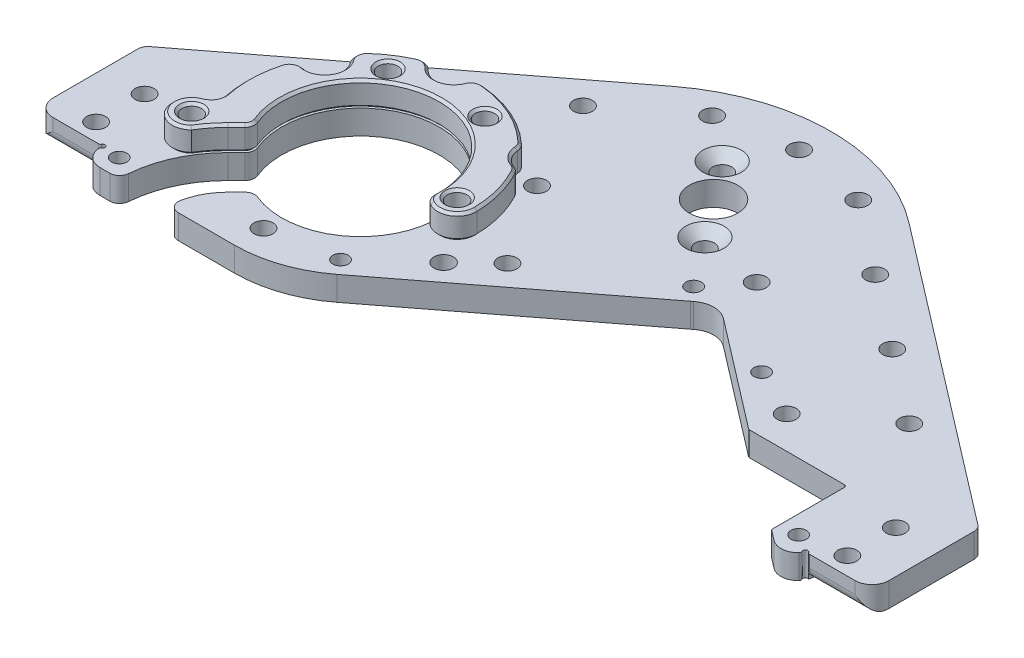
SolidWorks part; units mm, degrees
other "Weapon Motor Shock Spacer"
material "Alum Plate"
ref_plane "Front Plane" through (0, 0, 0) normal (0, 0, 1) x (1, 0, 0)
ref_plane "Top Plane" through (0, 0, 0) normal (0, 1, 0) x (1, 0, 0)
ref_plane "Right Plane" through (0, 0, 0) normal (1, 0, 0) x (0, 0, -1)
sketch "Top Layout" plane through (0, 0, 0) normal (0, 1, 0) x (1, 0, 0)
  line L0 (-114.046, -123.825) -> (-104.775, -123.825) construction
  line L1 (-104.775, -142.875) -> (-101.6, -142.875)
  line L2 (-104.775, -142.875) -> (-104.775, -104.775)
  line L3 (-104.775, -104.775) -> (-101.6, -104.775)
  line L4 (-101.6, -142.875) -> (-101.6, -104.775)
  line L5 (-104.775, -142.875) -> (-101.6, -104.775) construction
  line L6 (-104.775, -104.775) -> (-101.6, -142.875) construction
  line L7 (-19.05, -105.8164) -> (-101.6, -105.8164)
  line L8 (-19.05, -105.8164) -> (-19.05, -141.8336)
  line L9 (-19.05, -141.8336) -> (-101.6, -141.8336)
  line L10 (-101.6, -105.8164) -> (-101.6, -141.8336)
  line L11 (-19.05, -105.8164) -> (-101.6, -141.8336) construction
  line L12 (-19.05, -141.8336) -> (-101.6, -105.8164) construction
  line L13 (-133.096, -85.725) -> (-114.046, -85.725)
  line L14 (-133.096, -85.725) -> (-133.096, -161.925)
  line L15 (-133.096, -161.925) -> (-114.046, -161.925)
  line L16 (-114.046, -85.725) -> (-114.046, -161.925)
  line L17 (-133.096, -85.725) -> (-114.046, -161.925) construction
  line L18 (-133.096, -161.925) -> (-114.046, -85.725) construction
  line L19 (-104.775, -123.825) -> (0, -123.825) construction
  line L20 (0, -123.825) -> (0, 0) construction
  line L21 (-52.3528, -40.1717) -> (0, 0) construction
  line L22 (-70.6449, -16.3328) -> (-18.2922, 23.8388)
  line L23 (-34.0606, -64.0105) -> (18.2922, -23.8388)
  line L24 (-30.9251, 40.3023) -> (-122.2248, -29.7544)
  line L25 (-153.9748, -53.975) -> (-153.9748, -123.825)
  line L26 (-109.5248, -162.052) -> (109.5248, -162.052)
  line L27 (0, -162.052) -> (0, -123.825) construction
  line L28 (-109.5248, -162.052) -> (-109.5248, -20.0093) construction
  line L29 (-104.775, -142.875) -> (-104.775, -152.527)
  line L30 (-104.775, -152.527) -> (104.775, -152.527)
  line L31 (104.775, -104.775) -> (101.6, -104.775)
  line L32 (-144.4498, -73.025) -> (-109.5248, -73.025)
  line L33 (-144.4498, -73.025) -> (-144.4498, -123.825)
  line L34 (-144.4498, -123.825) -> (-109.5248, -123.825) construction
  line L35 (-109.5248, -73.025) -> (-109.5248, -162.052)
  line L36 (-144.4498, -73.025) -> (-109.5248, -123.825) construction
  line L37 (-144.4498, -123.825) -> (-109.5248, -73.025) construction
  line L38 (101.6, -142.875) -> (101.6, -104.775)
  line L39 (104.775, -142.875) -> (101.6, -142.875)
  line L40 (104.775, -142.875) -> (104.775, -104.775)
  line L41 (104.775, -142.875) -> (104.775, -152.527)
  line L42 (109.5248, -162.052) -> (109.5248, -20.0093) construction
  line L43 (30.9251, 40.3023) -> (122.2248, -29.7544)
  line L45 (19.05, -141.8336) -> (101.6, -141.8336)
  line L46 (101.6, -105.8164) -> (101.6, -141.8336)
  line L47 (19.05, -105.8164) -> (101.6, -105.8164)
  line L48 (19.05, -105.8164) -> (19.05, -141.8336)
  line L49 (133.096, -161.925) -> (114.046, -161.925)
  line L50 (114.046, -85.725) -> (114.046, -161.925)
  line L51 (133.096, -85.725) -> (114.046, -85.725)
  line L52 (133.096, -85.725) -> (133.096, -161.925)
  line L53 (144.4498, -123.825) -> (109.5248, -123.825) construction
  line L54 (109.5248, -73.025) -> (109.5248, -162.052)
  line L55 (144.4498, -73.025) -> (109.5248, -73.025)
  line L56 (144.4498, -73.025) -> (144.4498, -123.825)
  line L57 (-109.5248, -123.825) -> (-109.5248, -162.052) construction
  line L62 (-153.9748, -53.975) -> (-122.2248, -53.975)
  line L63 (-122.2248, -53.975) -> (-122.2248, -29.7544)
  line L64 (-144.4498, -123.825) -> (-153.9748, -123.825)
  line L65 (153.9748, -53.975) -> (153.9748, -123.825)
  line L66 (109.5248, -123.825) -> (109.5248, -162.052) construction
  line L67 (144.4498, -123.825) -> (153.9748, -123.825)
  line L68 (122.2248, -29.7544) -> (122.2248, -53.975)
  line L73 (-104.775, -104.775) -> (-104.775, -16.3647) construction
  line L74 (-95.25, -162.052) -> (-95.25, -9.0559) construction
  line L75 (-109.5248, -162.052) -> (-109.5248, -123.825) construction
  line L76 (109.5248, -162.052) -> (109.5248, -123.825) construction
  line L77 (122.2248, -53.975) -> (153.9748, -53.975)
  line L83 (104.775, -155.5496) -> (-104.775, -155.5496) construction
  line L88 (95.25, -162.052) -> (95.25, -9.0559) construction
  line L89 (104.775, -104.775) -> (104.775, -16.3647) construction
  line L92 (-104.775, -152.527) -> (-104.775, -162.052) construction
  line L93 (-14.605, -76.327) -> (14.605, -76.327)
  line L94 (-14.605, -76.327) -> (-14.605, -152.527)
  line L95 (-14.605, -152.527) -> (14.605, -152.527)
  line L96 (14.605, -76.327) -> (14.605, -152.527)
  line L97 (-14.605, -76.327) -> (14.605, -152.527) construction
  line L98 (-14.605, -152.527) -> (14.605, -76.327) construction
  line L99 (104.775, -152.527) -> (104.775, -162.052) construction
  line L100 (-19.05, -105.8164) -> (0, -105.8164) construction
  line L107 (0, -105.8164) -> (19.05, -105.8164) construction
  line L108 (104.775, -123.825) -> (114.046, -123.825) construction
  circle A0 centre (0, 0) radius 114.3
  circle A1 centre (0, 0) radius 6.35
  circle A2 centre (-52.3528, -40.1717) radius 17.8
  circle A3 centre (0, 0) radius 30.0482
  circle A4 centre (-52.3528, -40.1717) radius 30.0482
  arc A5 (-30.9251, 40.3023) -> (30.9251, 40.3023) centre (0, 0) cw
  point P2 (-103.1875, -123.825)
  point P7 (-60.325, -123.825)
  point P12 (-123.571, -123.825)
  point P30 (-126.9873, -98.425)
  point P35 (0, -114.427)
  point P53 (0, -152.527)
  dimension "D1" = 35.6
  dimension "D2" = 12.7
  dimension "D3" = 228.6
  dimension "D11" = 60.0964
  dimension "D12" = 50.8
  dimension "D14" = 52.5
  dimension "D4" = 3.175
  dimension "D5" = 19.05
  dimension "D6" = 76.2
  dimension "D7" = 82.55
  dimension "D8" = 38.1
  dimension "D9" = 104.775
  dimension "D10" = 18.0086
  dimension "D13" = 9.525
  dimension "D15" = 4.7498
  dimension "D16" = 9.525
  dimension "D17" = 9.652
  dimension "D18" = 50.8
  dimension "D19" = 12.446
  dimension "D20" = 65.9892
  dimension "D21" = 19.05
  dimension "D22" = 34.925
  dimension "D23" = 123.825
  dimension "D24" = 12.7
  dimension "D25" = 9.525
  dimension "D26" = 29.21
  dimension "D27" = 76.2
  dimension "D28" = 3.0226
sketch "Side Layout" plane through (0, 0, 0) normal (1, 0, 0) x (0, 0, -1)
  line L0 (0, -38.1) -> (0, 33.7344) construction
  line L1 (-114.3, -20.955) -> (114.3, -20.955)
  line L2 (-114.3, -20.955) -> (-114.3, -33.655)
  line L3 (-114.3, -33.655) -> (114.3, -33.655)
  line L4 (114.3, -20.955) -> (114.3, -33.655)
  line L5 (-114.3, -20.955) -> (114.3, -33.655) construction
  line L6 (-114.3, -33.655) -> (114.3, -20.955) construction
  line L7 (-9.525, -32.9406) -> (9.525, -32.9406)
  line L8 (-9.525, -32.9406) -> (-9.525, -38.1)
  line L9 (-9.525, -38.1) -> (9.525, -38.1)
  line L10 (9.525, -32.9406) -> (9.525, -38.1)
  line L11 (-9.525, -32.9406) -> (9.525, -38.1) construction
  line L12 (-9.525, -38.1) -> (9.525, -32.9406) construction
  line L13 (-11.9126, -29.3338) -> (11.9126, -29.3338)
  line L14 (-11.9126, -29.3338) -> (-11.9126, -32.9406)
  line L15 (-11.9126, -32.9406) -> (11.9126, -32.9406)
  line L16 (11.9126, -29.3338) -> (11.9126, -32.9406)
  line L17 (-11.9126, -29.3338) -> (11.9126, -32.9406) construction
  line L18 (-11.9126, -32.9406) -> (11.9126, -29.3338) construction
  line L19 (-6.35, -32.9406) -> (6.35, -32.9406)
  line L20 (-6.35, -32.9406) -> (-6.35, 33.7344)
  line L21 (-6.35, 33.7344) -> (6.35, 33.7344)
  line L22 (6.35, -32.9406) -> (6.35, 33.7344)
  line L23 (-6.35, -32.9406) -> (6.35, 33.7344) construction
  line L24 (-6.35, 33.7344) -> (6.35, -32.9406) construction
  line L25 (-162.052, 0) -> (-123.825, 0) construction
  line L26 (114.3, -33.655) -> (114.3, 0) construction
  line L27 (-142.875, 19.05) -> (-104.775, 19.05)
  line L28 (-40.1717, -9.525) -> (-40.1717, 5.4) construction
  line L29 (-142.875, 19.05) -> (-142.875, -19.05)
  line L30 (-142.875, -19.05) -> (-104.775, -19.05)
  line L31 (-104.775, 19.05) -> (-104.775, -19.05)
  line L32 (-142.875, 19.05) -> (-104.775, -19.05) construction
  line L33 (-142.875, -19.05) -> (-104.775, 19.05) construction
  line L34 (-130.175, -38.1) -> (-117.9516, -38.1) construction
  line L35 (-57.9717, -14.6) -> (-22.3717, -14.6)
  line L36 (-30.0482, -2.794) -> (30.0482, -2.794)
  line L37 (-30.0482, -2.794) -> (-30.0482, -20.955)
  line L38 (-30.0482, -20.955) -> (30.0482, -20.955)
  line L39 (30.0482, -2.794) -> (30.0482, -20.955)
  line L40 (-30.0482, -2.794) -> (30.0482, -20.955) construction
  line L41 (-30.0482, -20.955) -> (30.0482, -2.794) construction
  line L42 (-30.0482, -2.794) -> (-30.0482, 0) construction
  line L43 (-123.825, 0) -> (0, 0) construction
  line L44 (-57.9717, -14.6) -> (-57.9717, 25.4)
  line L45 (-57.9717, 25.4) -> (-22.3717, 25.4)
  line L46 (-22.3717, -14.6) -> (-22.3717, 25.4)
  line L47 (-19.05, 0) -> (19.05, 0)
  line L48 (-19.05, 0) -> (-19.05, -1.9812)
  line L49 (-19.05, -1.9812) -> (19.05, -1.9812)
  line L50 (19.05, 0) -> (19.05, -1.9812)
  line L51 (-19.05, 0) -> (19.05, -1.9812) construction
  line L52 (-19.05, -1.9812) -> (19.05, 0) construction
  line L53 (-70.2199, -3.175) -> (-10.1235, -3.175)
  line L54 (-70.2199, -3.175) -> (-70.2199, -15.875)
  line L55 (-70.2199, -15.875) -> (-10.1235, -15.875)
  line L56 (-10.1235, -3.175) -> (-10.1235, -15.875)
  line L57 (-70.2199, -3.175) -> (-10.1235, -15.875) construction
  line L58 (-70.2199, -15.875) -> (-10.1235, -3.175) construction
  line L59 (-40.1717, -9.525) -> (-40.1717, 0) construction
  line L60 (-57.9717, -14.6) -> (-22.3717, 25.4) construction
  line L61 (-57.9717, 25.4) -> (-22.3717, -14.6) construction
  line L62 (-22.3717, 0) -> (-57.9717, 0) construction
  line L63 (-137.8162, 0) -> (-123.825, -13.9912) construction
  line L64 (-139.065, 15.24) -> (-108.585, 15.24) construction
  line L65 (-139.065, 15.24) -> (-139.065, -15.24) construction
  line L66 (-139.065, -15.24) -> (-108.585, -15.24) construction
  line L67 (-108.585, 15.24) -> (-108.585, -15.24) construction
  line L68 (-139.065, 15.24) -> (-108.585, -15.24) construction
  line L69 (-139.065, -15.24) -> (-108.585, 15.24) construction
  line L70 (-137.8162, 0) -> (-123.825, 13.9912) construction
  line L71 (-123.825, -13.9912) -> (-109.8338, 0) construction
  line L72 (-123.825, 13.9912) -> (-109.8338, 0) construction
  line L73 (-137.8162, 0) -> (-109.8338, 0) construction
  line L74 (-123.825, -13.9912) -> (-123.825, 13.9912) construction
  line L75 (-6.35, 17.8594) -> (6.35, 17.8594)
  line L76 (114.3, 0) -> (-114.3, 0) construction
  line L77 (-22.3717, 19.05) -> (-6.35, 19.05) construction
  line L78 (-123.825, 38.1) -> (-97.9206, 38.1) construction
  line L79 (-19.05, -3.5814) -> (19.05, -3.5814)
  line L80 (-19.05, -3.5814) -> (-19.05, -1.9812)
  line L81 (-19.05, -1.9812) -> (19.05, -1.9812)
  line L82 (19.05, -3.5814) -> (19.05, -1.9812)
  line L83 (-19.05, -3.5814) -> (19.05, -1.9812) construction
  line L84 (-19.05, -1.9812) -> (19.05, -3.5814) construction
  line L85 (-8.7376, -16.7608) -> (8.7376, -16.7608)
  line L86 (-8.7376, -16.7608) -> (-8.7376, -29.3338)
  line L87 (-8.7376, -29.3338) -> (8.7376, -29.3338)
  line L88 (8.7376, -16.7608) -> (8.7376, -29.3338)
  line L89 (-8.7376, -16.7608) -> (8.7376, -29.3338) construction
  line L90 (-8.7376, -29.3338) -> (8.7376, -16.7608) construction
  line L91 (-8.7376, -3.5814) -> (8.7376, -3.5814)
  line L92 (-8.7376, -3.5814) -> (-8.7376, -16.1544)
  line L93 (-8.7376, -16.1544) -> (8.7376, -16.1544)
  line L94 (8.7376, -3.5814) -> (8.7376, -16.1544)
  line L95 (-8.7376, -3.5814) -> (8.7376, -16.1544) construction
  line L96 (-8.7376, -16.1544) -> (8.7376, -3.5814) construction
  circle A0 centre (-123.825, 0) radius 18.0086
  circle A1 centre (-123.825, 0) radius 38.1
  circle A2 centre (-139.065, 15.24) radius 1.905
  circle A3 centre (-108.585, 15.24) radius 1.905
  circle A4 centre (-108.585, -15.24) radius 1.905
  circle A5 centre (-139.065, -15.24) radius 1.905
  circle A6 centre (-137.8162, 0) radius 1.6002
  circle A7 centre (-123.825, 13.9912) radius 1.6002
  circle A8 centre (-109.8338, 0) radius 1.6002
  circle A9 centre (-123.825, -13.9912) radius 1.6002
  point P0 (0, -27.305)
  point P6 (0, -31.1372)
  point P7 (0, -35.5203)
  point P21 (0, 0.3969)
  point P32 (0, -11.8745)
  point P43 (0, -0.9906)
  point P55 (-40.1717, -9.525)
  point P72 (-40.1717, 5.4)
  point P88 (0, -23.0473)
  point P93 (0, -2.7813)
  point P102 (0, -9.8679)
  dimension "D17" = 3.81
  dimension "D18" = 3.2004
  dimension "D1" = 12.7
  dimension "D2" = 5.1594
  dimension "D3" = 19.05
  dimension "D4" = 3.6068
  dimension "D5" = 23.8252
  dimension "D6" = 12.7
  dimension "D7" = 18.161
  dimension "D8" = 1.9812
  dimension "D9" = 12.7
  dimension "D10" = 40
  dimension "D11" = 25.4
  dimension "D12" = 50.8
  dimension "D13" = 41.275
  dimension "D14" = 30.48
  dimension "D15" = 4.445
  dimension "D16" = 19.7866
  dimension "D19" = 15.875
  dimension "D20" = 6.35
  dimension "D21" = 38.1
  dimension "D22" = 1.6002
  dimension "D23" = 38.1
  dimension "D24" = 17.4752
  dimension "D25" = 12.573
ref_plane "Plane1" through (0, 25.4, 0) normal (0, 1, 0) x (1, 0, 0)
sketch "Sketch3" plane through (0, 25.4, 0) normal (0, 1, 0) x (1, 0, 0)
  line L0 (-104.775, -36.3747) -> (-30.9251, 20.2924)
  line L1 (-104.775, -104.775) -> (-104.775, -16.3647) construction
  line L2 (0, -200130.175) -> (0, 199882.0484) construction
  line L3 (-30.9251, 40.3023) -> (-122.2248, -29.7544) construction
  line L5 (-104.775, -36.3747) -> (-104.775, -77.6497)
  line L6 (-92.075, -77.6497) -> (-104.775, -77.6497)
  line L7 (30.9251, 20.2924) -> (104.775, -36.3747)
  line L8 (104.775, -77.6497) -> (92.075, -77.6497)
  line L9 (104.775, -36.3747) -> (104.775, -77.6497)
  line L11 (104.775, -104.775) -> (104.775, -16.3647) construction
  line L12 (30.9251, 40.3023) -> (122.2248, -29.7544) construction
  line L13 (92.075, -74.6536) -> (24.1423, -22.5271)
  line L14 (-32.2514, -66.3682) -> (20.1013, -26.1965)
  line L15 (-30.9251, 20.2924) -> (0, 44.022)
  line L16 (0, 44.022) -> (30.9251, 20.2924)
  line L17 (-92.075, -77.6497) -> (-92.075, -73.1917)
  line L19 (-92.075, -73.1917) -> (-52.3528, -73.1917)
  line L20 (92.075, -74.6536) -> (92.075, -77.6497)
  circle A1 centre (-52.3528, -40.1717) radius 20.6375
  circle A2 centre (0, 0) radius 6.35
  circle A3 centre (0, 0) radius 6.35 construction
  arc A4 (-52.3528, -73.1917) -> (-32.2514, -66.3682) centre (-52.3528, -40.1717) ccw
  arc A5 (20.1013, -26.1965) -> (24.1423, -22.5271) centre (0, 0) ccw
  arc A6 (30.9251, 20.2924) -> (-30.9251, 20.2924) centre (0, -20.01) ccw construction
  point P28 (0, 44.022)
  dimension "D1" = 33.02
  dimension "D5" = 50.8
  dimension "D7" = 41.275
  dimension "D2" = 41.275
  dimension "D3" = 34.925
  dimension "D4" = 12.7
  dimension "D6" = 38.1
extrude "Boss-Extrude1" add sketch "Sketch3" against normal blind 6.35
ref_plane "Plane3" through (-104.775, 0, 0) normal (-1, 0, 0) x (0, 0, 1)
sketch "Sketch6" plane through (-104.775, 0, 0) normal (-1, 0, 0) x (0, 0, 1)
  line L0 (162.052, -25.4) -> (162.052, 25.4)
  line L1 (162.052, 25.4) -> (77.6497, 25.4)
  line L2 (36.3747, 25.4) -> (77.6497, 25.4) construction
  line L3 (147.7645, 11.1125) -> (162.052, 11.1125) construction
  line L4 (162.052, 0) -> (71.2997, 0) construction
  line L5 (77.6497, 25.4) -> (77.6497, 19.05)
  line L6 (77.6497, 19.05) -> (36.3747, 19.05)
  line L7 (36.3747, 19.05) -> (36.3747, 6.35)
  line L8 (36.3747, 6.35) -> (71.2997, 6.35)
  line L10 (99.6315, -3.175) -> (99.6315, 11.1125) construction
  line L11 (71.2997, -25.4) -> (162.052, -25.4)
  line L13 (71.2997, 6.35) -> (71.2997, -25.4)
  line L14 (152.527, -25.4) -> (152.527, 25.4) construction
  line L15 (99.6315, 11.1125) -> (99.6315, 25.4) construction
  line L16 (147.7645, 11.1125) -> (147.7645, 25.4) construction
  line L17 (94.869, -7.9375) -> (104.394, -7.9375) construction
  line L18 (94.869, -7.9375) -> (94.869, 25.4) construction
  line L19 (94.869, 25.4) -> (104.394, 25.4) construction
  line L20 (104.394, -7.9375) -> (104.394, 25.4) construction
  line L21 (94.869, -7.9375) -> (104.394, 25.4) construction
  line L22 (94.869, 25.4) -> (104.394, -7.9375) construction
  line L23 (147.7645, 11.1125) -> (147.7645, -3.175) construction
  line L24 (104.394, -7.9375) -> (123.825, -7.9375) construction
  line L25 (143.002, -7.9375) -> (152.527, -7.9375) construction
  line L26 (143.002, -7.9375) -> (143.002, 25.4) construction
  line L27 (143.002, 25.4) -> (152.527, 25.4) construction
  line L28 (152.527, -7.9375) -> (152.527, 25.4) construction
  line L29 (143.002, -7.9375) -> (152.527, 25.4) construction
  line L30 (143.002, 25.4) -> (152.527, -7.9375) construction
  line L31 (123.825, -7.9375) -> (152.527, -7.9375) construction
  line L32 (104.775, 19.05) -> (104.775, -19.05) construction
  line L34 (155.702, -25.4) -> (155.702, 25.4) construction
  circle A0 centre (109.8338, 0) radius 1.6002 construction
  circle A1 centre (123.825, 13.9912) radius 1.6002 construction
  circle A2 centre (137.8162, 0) radius 1.6002 construction
  circle A3 centre (123.825, -13.9912) radius 1.6002 construction
  circle A4 centre (109.8338, 0) radius 1.6002 construction
  circle A5 centre (123.825, 13.9912) radius 1.6002 construction
  circle A6 centre (137.8162, 0) radius 1.6002 construction
  circle A7 centre (123.825, -13.9912) radius 1.6002 construction
  circle A8 centre (123.825, 0) radius 18.0086 construction
  circle A9 centre (123.825, 0) radius 18.0086 construction
  circle A10 centre (123.825, 0) radius 9.525
  circle A11 centre (108.585, -15.24) radius 1.905 construction
  circle A12 centre (108.585, 15.24) radius 1.905 construction
  circle A13 centre (139.065, 15.24) radius 1.905 construction
  circle A14 centre (139.065, -15.24) radius 1.905 construction
  circle A15 centre (108.585, -15.24) radius 1.905
  circle A16 centre (108.585, 15.24) radius 1.905
  circle A17 centre (139.065, 15.24) radius 1.905
  circle A18 centre (139.065, -15.24) radius 1.905
  circle A19 centre (147.7645, 11.1125) radius 2.5527
  circle A26 centre (99.6315, 11.1125) radius 2.5527
  circle A27 centre (99.6315, -3.175) radius 2.5527
  circle A28 centre (147.7645, -3.175) radius 2.5527
  point P29 (0, 0)
  point P55 (99.6315, 8.7312)
  point P61 (147.7645, 8.7312)
  dimension "D4" = 19.05
  dimension "D7" = 5.1054
  dimension "D1" = 6.35
  dimension "D2" = 12.7
  dimension "D3" = 25.4
  dimension "D5" = 6.35
  dimension "D6" = 3.175
  dimension "D8" = 0.381
  dimension "D9" = 14.2875
  dimension "D10" = 9.525
  dimension "D12" = 33.3375
sketch "Sketch12" [suppressed] plane through (0, 19.05, 0) normal (0, 1, 0) x (1, 0, 0)
  line L0 (-104.775, -77.6497) -> (-104.775, -36.3747)
  line L1 (-104.775, -36.3747) -> (-92.075, -36.3747)
  line L3 (-92.075, -36.3747) -> (-92.075, -77.6497)
  line L5 (-92.075, -77.6497) -> (-104.775, -77.6497)
  line L6 (-98.425, -77.6497) -> (-98.425, -63.3622) construction
  line L7 (-98.425, -63.3622) -> (-98.425, -50.6622) construction
  line L8 (-98.425, -50.6622) -> (-98.425, -36.3747) construction
  line L10 (-98.425, -36.3747) -> (-104.775, -36.3747) construction
  circle A0 centre (-98.425, -63.3622) radius 2.5527
  circle A1 centre (-98.425, -50.6622) radius 2.5527
  dimension "D2" = 5.1054
  dimension "D1" = 12.7
  dimension "D3" = 12.7
sketch "Sketch8" plane through (0, 25.4, 0) normal (0, 1, 0) x (1, 0, 0)
  line L0 (-109.5248, -162.052) -> (-109.5248, -20.0093) construction
  line L1 (-104.775, -77.6497) -> (-109.5248, -77.6497)
  line L2 (-104.775, -77.6497) -> (-104.775, -36.3747)
  line L3 (-104.775, -36.3747) -> (-109.5248, -36.3747)
  line L4 (-109.5248, -77.6497) -> (-109.5248, -36.3747)
  line L5 (-104.775, -77.6497) -> (-109.5248, -36.3747) construction
  line L6 (-104.775, -36.3747) -> (-109.5248, -77.6497) construction
  line L7 (104.775, -77.6497) -> (109.5248, -77.6497)
  line L8 (104.775, -77.6497) -> (104.775, -36.3747)
  line L9 (104.775, -36.3747) -> (109.5248, -36.3747)
  line L10 (109.5248, -77.6497) -> (109.5248, -36.3747)
  line L11 (104.775, -77.6497) -> (109.5248, -36.3747) construction
  line L12 (104.775, -36.3747) -> (109.5248, -77.6497) construction
  point P4 (-107.1499, -57.0122)
  point P10 (107.1499, -57.0122)
extrude "Boss-Extrude4" add sketch "Sketch8" against normal through all
sketch "Sketch9" plane through (0, 25.4, 0) normal (0, 1, 0) x (1, 0, 0)
  line L0 (7.4916, -9.7632) -> (0, 0) construction
  line L1 (0, 0) -> (-7.4916, 9.7632) construction
  line L2 (0, 44.022) -> (-104.775, -36.3747) construction
  circle A0 centre (-7.4916, 9.7632) radius 2.4892
  circle A1 centre (7.4916, -9.7632) radius 2.4892
  dimension "D2" = 4.9784
  dimension "D1" = 24.6126
extrude "Collar Holes" cut sketch "Sketch9" against normal through all
sketch "Sketch10" plane through (0, 25.4, 0) normal (0, 1, 0) x (1, 0, 0)
  line L0 (0, 33.4567) -> (0, 30.79) construction
  line L1 (-5.1026, 40.1066) -> (0, 33.4567) construction
  line L2 (0, 33.4567) -> (5.1026, 40.1066) construction
  line L3 (0, 44.022) -> (-104.775, -36.3747) construction
  line L4 (104.775, -36.3747) -> (0, 44.022) construction
  circle A0 centre (0, 33.4567) radius 4.7625 construction
  circle A1 centre (0, 33.4567) radius 2.0193
  arc A3 (30.9251, 20.2924) -> (-30.9251, 20.2924) centre (0, -20.01) ccw construction
  dimension "D2" = 9.525
  dimension "D3" = 4.0386
  dimension "D1" = 8.382
extrude "Spacer Holes" cut sketch "Sketch10" against normal through all
pattern_linear "Spacer Hole Pattern" count 5 spacing 24.13 along (-0.7934, 0, 0.6088) of "Spacer Holes"
mirror "Spacer Hole Mirror" about plane through (0, 0, 0) normal (1, 0, 0) of "Spacer Hole Pattern"
sketch "Sketch16" plane through (0, 25.4, 0) normal (0, 1, 0) x (1, 0, 0)
  line L0 (-109.5248, -50.6622) -> (-98.425, -50.6622) construction
  line L1 (-109.5248, -36.3747) -> (-109.5248, -77.6497) construction
  line L2 (-98.425, -50.6622) -> (-98.425, -63.3622) construction
  line L3 (-98.425, -63.3622) -> (-109.5248, -63.3622) construction
  line L4 (-98.425, -63.3622) -> (-98.425, -77.6497) construction
  line L5 (-109.5248, -77.6497) -> (-92.075, -77.6497) construction
  line L6 (-98.425, -50.6622) -> (-98.425, -36.3747) construction
  line L7 (-104.775, -36.3747) -> (-109.5248, -36.3747) construction
  line L8 (-104.775, -36.3747) -> (-104.775, -77.6497) construction
  line L9 (0, 0) -> (0, 30.79) construction
  line L10 (104.775, -36.3747) -> (104.775, -77.6497) construction
  circle A0 centre (-98.425, -50.6622) radius 2.0193
  circle A1 centre (-98.425, -63.3622) radius 2.0193
  circle A4 centre (98.425, -63.3622) radius 2.0193
  circle A5 centre (98.425, -50.6622) radius 2.0193
  arc A6 (30.9251, 20.2924) -> (-30.9251, 20.2924) centre (0, -20.01) ccw construction
  dimension "D1" = 4.0386
  dimension "D2" = 12.7
  dimension "D3" = 6.35
extrude "Custom Nutstrip Holes" cut sketch "Sketch16" against normal through all
sketch "Sketch36" plane through (0, 25.4, 0) normal (0, 1, 0) x (1, 0, 0)
  line L0 (-52.3528, -65.5717) -> (-12.44, -41.5615) construction
  line L1 (-12.44, -41.5615) -> (24.5129, -13.2066) construction
  line L2 (24.5129, -13.2066) -> (58.2939, -39.1277) construction
  line L3 (-32.2514, -66.3682) -> (20.1013, -26.1965) construction
  line L4 (24.1423, -22.5271) -> (92.075, -74.6536) construction
  line L5 (-12.44, -41.5615) -> (-7.8012, -47.6069) construction
  line L6 (58.2939, -39.1277) -> (53.6552, -45.1731) construction
  line L7 (-52.3528, -65.5717) -> (-52.3528, -40.1717) construction
  line L8 (58.2939, -39.1277) -> (92.075, -65.0488) construction
  line L9 (92.075, -65.0488) -> (92.075, -77.6497) construction
  line L10 (-52.3528, -40.1717) -> (-26.1764, -20.0858) construction
  line L11 (-26.1764, -20.0858) -> (0, 0) construction
  line L12 (92.075, -74.6536) -> (92.075, -77.6497) construction
  circle A0 centre (-52.3528, -65.5717) radius 2.0193
  circle A1 centre (58.2939, -39.1277) radius 2.0193
  circle A2 centre (24.5129, -13.2066) radius 2.0193
  circle A3 centre (-12.44, -41.5615) radius 2.0193
  circle A4 centre (-76.5745, -25.3009) radius 2.0193 construction
  circle A5 centre (-52.3528, -65.5717) radius 4.7625 construction
  circle A6 centre (-12.44, -41.5615) radius 4.7625 construction
  circle A7 centre (24.5129, -13.2066) radius 4.7625 construction
  circle A8 centre (58.2939, -39.1277) radius 4.7625 construction
  arc A9 (-52.3528, -73.1917) -> (-32.2514, -66.3682) centre (-52.3528, -40.1717) ccw construction
  circle A10 centre (-26.1764, -20.0858) radius 2.0193
  dimension "D1" = 9.525
  dimension "D2" = 25.4
  dimension "D3" = 7.62
extrude "Aux Spacer Holes" cut sketch "Sketch36" against normal through all
sketch "Sketch38" [suppressed] plane through (-104.775, 0, 0) normal (-1, 0, 0) x (0, 0, 1)
  line L1 (152.527, -7.9375) -> (143.002, -7.9375)
  line L2 (152.527, -7.9375) -> (152.527, 25.4)
  line L3 (152.527, 25.4) -> (143.002, 25.4)
  line L4 (143.002, -7.9375) -> (143.002, 25.4)
  line L5 (152.527, -7.9375) -> (143.002, 25.4) construction
  line L6 (152.527, 25.4) -> (143.002, -7.9375) construction
  point P4 (147.7645, 8.7312)
extrude "Cut-Extrude16" [suppressed] cut sketch "Sketch38" against normal blind 9.525
sketch "Sketch46" [suppressed] plane through (-104.775, 0, 0) normal (-1, 0, 0) x (0, 0, 1)
  line L0 (142.875, 19.05) -> (104.775, -19.05) construction
  line L1 (104.14, 19.685) -> (143.51, 19.685)
  line L2 (104.14, 19.685) -> (104.14, -19.685)
  line L3 (104.14, -19.685) -> (143.51, -19.685)
  line L4 (143.51, 19.685) -> (143.51, -19.685)
  line L5 (104.14, 19.685) -> (143.51, -19.685) construction
  line L6 (104.14, -19.685) -> (143.51, 19.685) construction
  point P0 (123.825, 0)
  dimension "D1" = 39.37
extrude "Cut-Extrude21" [suppressed] cut sketch "Sketch46" against normal blind 6.985
ref_plane "Plane5" through (0, 0, 152.527) normal (0, 0, 1) x (1, 0, 0)
sketch "Sketch41" plane through (0, 0, 152.527) normal (0, 0, 1) x (1, 0, 0)
  line L0 (-104.775, -7.9375) -> (-104.775, 25.4) construction
  line L1 (-104.775, -7.9375) -> (-104.775, 12.7)
  line L2 (-104.775, -7.9375) -> (104.775, -7.9375)
  line L3 (104.775, -7.9375) -> (104.775, 12.7)
  line L4 (104.775, 25.4) -> (-104.775, 25.4)
  line L5 (0, -7.9375) -> (0, 25.4) construction
  line L6 (-104.775, 3.9624) -> (-100.0125, 3.9624) construction
  line L7 (-100.0125, 3.9624) -> (-100.0125, 25.4) construction
  line L8 (104.775, 3.9624) -> (100.0125, 3.9624) construction
  line L9 (100.0125, 3.9624) -> (100.0125, 25.4) construction
  line L10 (19.05, 20.6375) -> (23.8252, 20.6375) construction
  line L11 (19.05, 15.875) -> (78.5876, 15.875) construction
  line L12 (19.05, 15.875) -> (19.05, 25.4) construction
  line L13 (19.05, 25.4) -> (78.5876, 25.4) construction
  line L14 (78.5876, 15.875) -> (78.5876, 25.4) construction
  line L15 (19.05, 15.875) -> (78.5876, 25.4) construction
  line L16 (19.05, 25.4) -> (78.5876, 15.875) construction
  line L17 (23.8252, 20.6375) -> (38.1127, 20.6375) construction
  line L18 (38.1127, 20.6375) -> (52.4002, 20.6375) construction
  line L19 (52.4002, 20.6375) -> (66.6877, 20.6375) construction
  line L20 (-104.775, 25.4) -> (-112.395, 25.4)
  line L21 (-112.395, 25.4) -> (-112.395, 3.175)
  line L22 (-112.395, 3.175) -> (-109.5248, 3.175)
  line L23 (-109.5248, 3.175) -> (-109.5248, 12.7)
  line L24 (-109.5248, 12.7) -> (-104.775, 12.7)
  line L25 (-104.775, 12.7) -> (-104.775, 25.4) construction
  line L26 (104.775, 25.4) -> (112.395, 25.4)
  line L27 (112.395, 25.4) -> (112.395, 3.175)
  line L28 (112.395, 3.175) -> (109.5248, 3.175)
  line L29 (109.5248, 3.175) -> (109.5248, 12.7)
  line L30 (109.5248, 12.7) -> (104.775, 12.7)
  line L31 (104.775, 12.7) -> (104.775, 25.4) construction
  line L32 (-100.0125, 3.9624) -> (-87.3125, 3.9624) construction
  line L33 (-63.5, -1.5875) -> (0, -1.5875) construction
  line L34 (0, -1.5875) -> (63.5, -1.5875) construction
  line L35 (63.5, -1.5875) -> (63.5, -7.9375) construction
  circle A0 centre (-100.0125, 3.9624) radius 2.5527
  circle A1 centre (100.0125, 3.9624) radius 2.5527
  circle A2 centre (23.8252, 20.6375) radius 2.5527
  circle A3 centre (38.1127, 20.6375) radius 2.5527
  circle A4 centre (52.4002, 20.6375) radius 2.5527
  circle A5 centre (66.6877, 20.6375) radius 2.5527
  circle A6 centre (-66.6877, 20.6375) radius 2.5527
  circle A7 centre (-52.4002, 20.6375) radius 2.5527
  circle A8 centre (-38.1127, 20.6375) radius 2.5527
  circle A9 centre (-23.8252, 20.6375) radius 2.5527
  circle A10 centre (-87.3125, 3.9624) radius 2.5527
  circle A11 centre (87.3125, 3.9624) radius 2.5527
  circle A12 centre (-63.5, -1.5875) radius 2.5527
  circle A13 centre (63.5, -1.5875) radius 2.5527
  point P14 (48.8188, 20.6375)
  dimension "D3" = 5.1054
  dimension "D7" = 5.1054
  dimension "D1" = 21.4376
  dimension "D2" = 4.7625
  dimension "D4" = 9.525
  dimension "D5" = 59.5376
  dimension "D6" = 4.7752
  dimension "D8" = 14.2875
  dimension "D9" = 7.62
  dimension "D10" = 4.7498
  dimension "D11" = 12.7
  dimension "D12" = 9.525
  dimension "D13" = 19.05
  dimension "D14" = 12.7
  dimension "D15" = 6.35
  dimension "D16" = 63.5
sketch "Sketch43" [suppressed] plane through (-109.5248, 0, 0) normal (-1, 0, 0) x (0, 0, 1)
  line L1 (152.527, 12.7) -> (155.702, 12.7)
  line L2 (152.527, 12.7) -> (152.527, 25.4)
  line L3 (152.527, 25.4) -> (155.702, 25.4)
  line L4 (155.702, 12.7) -> (155.702, 25.4)
  line L5 (152.527, 12.7) -> (155.702, 25.4) construction
  line L6 (152.527, 25.4) -> (155.702, 12.7) construction
  line L7 (162.052, 25.4) -> (77.6497, 25.4) construction
  point P4 (154.1145, 19.05)
  dimension "D1" = 3.175
sketch "Sketch44" plane through (0, 25.4, 0) normal (0, 1, 0) x (1, 0, 0)
  line L0 (73.8315, -147.7645) -> (73.8315, -152.527) construction
  line L1 (92.075, -74.6536) -> (92.075, -77.6497) construction
  line L2 (-92.075, -77.6497) -> (-92.075, -73.1917) construction
  line L3 (0, -123.825) -> (0, 0) construction
  line L4 (-92.075, -73.1917) -> (-52.3528, -73.1917) construction
  line L5 (-104.775, -104.775) -> (-104.775, -16.3647) construction
  line L6 (-32.2514, -66.3682) -> (20.1013, -26.1965) construction
  line L21 (-104.775, -68.1247) -> (-104.775, -152.527)
  line L22 (-104.775, -152.527) -> (104.775, -152.527)
  line L23 (104.775, -152.527) -> (104.775, -68.1247)
  line L34 (-104.775, -99.6315) -> (-100.0125, -99.6315) construction
  line L35 (-104.775, -147.7645) -> (-100.0125, -147.7645) construction
  line L36 (0, -152.527) -> (0, -35.6178) construction
  line L38 (30.969, -147.7645) -> (45.2565, -147.7645) construction
  line L39 (45.2565, -147.7645) -> (59.544, -147.7645) construction
  line L40 (59.544, -147.7645) -> (73.8315, -147.7645) construction
  line L41 (23.8252, -152.527) -> (30.969, -152.527) construction
  line L42 (104.775, -152.527) -> (-104.775, -152.527) construction
  line L43 (30.969, -152.527) -> (38.1127, -152.527) construction
  line L44 (30.969, -152.527) -> (30.969, -147.7645) construction
  line L45 (-92.075, -77.6497) -> (-104.775, -77.6497) construction
  line L48 (-35.1507, -62.5899) -> (-8.9743, -42.504) construction
  line L49 (-8.9743, -42.504) -> (17.2021, -22.4182) construction
  line L50 (45.5313, -32.9364) -> (87.3125, -64.9962) construction
  line L51 (92.075, -74.6536) -> (24.1423, -22.5271) construction
  line L52 (104.775, -77.6497) -> (92.075, -77.6497) construction
  line L79 (-104.775, -68.1247) -> (-92.075, -68.1247)
  line L80 (-92.075, -68.1247) -> (-92.075, -63.6667)
  line L85 (21.8118, -8.7328) -> (92.075, -62.6476)
  line L86 (-38.0499, -58.8115) -> (14.3028, -18.6398)
  line L87 (-92.075, -63.6667) -> (-52.3528, -63.6667)
  line L88 (92.075, -62.6476) -> (92.075, -68.1247)
  line L89 (92.075, -68.1247) -> (104.775, -68.1247)
  circle A0 centre (-73.8315, -147.7645) radius 2.5527
  circle A1 centre (-59.544, -147.7645) radius 2.5527
  circle A2 centre (-45.2565, -147.7645) radius 2.5527
  circle A3 centre (-30.969, -147.7645) radius 2.5527
  circle A17 centre (-100.0125, -99.6315) radius 2.5527
  circle A18 centre (-100.0125, -147.7645) radius 2.5527
  circle A19 centre (100.0125, -147.7645) radius 2.5527
  circle A20 centre (100.0125, -99.6315) radius 2.5527
  circle A21 centre (30.969, -147.7645) radius 2.5527
  circle A22 centre (45.2565, -147.7645) radius 2.5527
  circle A23 centre (59.544, -147.7645) radius 2.5527
  circle A24 centre (73.8315, -147.7645) radius 2.5527
  circle A25 centre (-87.3125, -68.4292) radius 4.7625 construction
  circle A26 centre (-35.1507, -62.5899) radius 4.7625 construction
  circle A27 centre (-8.9743, -42.504) radius 4.7625 construction
  circle A28 centre (17.2021, -22.4182) radius 4.7625 construction
  circle A29 centre (45.5313, -32.9364) radius 4.7625 construction
  circle A30 centre (87.3125, -64.9962) radius 4.7625 construction
  circle A32 centre (-87.3125, -68.4292) radius 2.5527
  circle A33 centre (-35.1507, -62.5899) radius 2.5527
  circle A34 centre (-8.9743, -42.504) radius 2.5527 construction
  circle A35 centre (17.2021, -22.4182) radius 2.5527
  circle A36 centre (45.5313, -32.9364) radius 2.5527
  circle A37 centre (87.3125, -64.9962) radius 2.5527
  circle A38 centre (-97.155, -85.2697) radius 7.62 construction
  circle A39 centre (97.155, -85.2697) radius 7.62 construction
  circle A40 centre (24.5121, -32.4156) radius 7.62 construction
  arc A41 (20.1013, -26.1965) -> (24.1423, -22.5271) centre (0, 0) ccw construction
  circle A42 centre (-97.155, -85.2697) radius 2.5527
  circle A43 centre (24.5121, -32.4156) radius 2.5527
  circle A44 centre (97.155, -85.2697) radius 2.5527
  arc A56 (14.3028, -18.6398) -> (21.8118, -8.7328) centre (0, 0) ccw
  arc A57 (-52.3528, -63.6667) -> (-38.0499, -58.8115) centre (-52.3528, -40.1717) ccw
  point P4 (-104.775, -152.527)
  dimension "D2" = 5.1054
  dimension "D7" = 5.1054
  dimension "D8" = 15.24
  dimension "D3" = 9.525
  dimension "D9" = 9.525
  dimension "D4" = 4.7625
  dimension "D5" = 14.2875
  dimension "D6" = 9.525
  dimension "D1" = 4.7625
  dimension "D10" = 52.664
sketch "Sketch82" [suppressed] plane through (0, 28.829, 0) normal (0, 1, 0) x (1, 0, 0)
  line L0 (-52.3528, -63.6667) -> (-92.075, -63.6667) construction
  line L1 (-52.3528, -65.5717) -> (-52.3528, -63.6667) construction
  line L2 (-12.4467, -41.5667) -> (-13.6064, -40.0553) construction
  line L3 (14.3028, -18.6398) -> (-38.0499, -58.8115) construction
  line L4 (24.5175, -13.2101) -> (25.6772, -11.6988) construction
  line L5 (92.075, -62.6476) -> (21.8118, -8.7328) construction
  line L6 (58.2962, -39.1295) -> (59.4559, -37.6181) construction
  line L7 (21.4643, -9.5551) -> (21.8118, -8.7328)
  line L8 (21.8118, -8.7328) -> (22.2143, -9.0416)
  circle A0 centre (-52.3528, -65.5717) radius 4.7625
  circle A1 centre (-12.4467, -41.5667) radius 4.7625
  arc A2 (21.4643, -9.5551) -> (22.2143, -9.0416) centre (24.5175, -13.2101) ccw
  circle A3 centre (58.2962, -39.1295) radius 4.7625
  arc A4 (14.3028, -18.6398) -> (21.8118, -8.7328) centre (0, 0) ccw construction
  dimension "D1" = 9.525
  dimension "D2" = 1.905
  dimension "D3" = 30.8104
  dimension "D4" = 83.6926
  dimension "D5" = 41.1154
extrude "Cut-Extrude38" [suppressed] cut sketch "Sketch82" against normal up to surface (3.429 mm away)
sketch "Sketch45" [suppressed] plane through (0, -25.4, 0) normal (0, -1, 0) x (1, 0, 0)
  circle A2 centre (24.5121, 32.4156) radius 6.35
  circle A4 centre (-97.155, 85.2697) radius 6.35
  circle A5 centre (97.155, 85.2697) radius 6.35
  dimension "D1" = 12.7
ref_plane "Plane6" through (0, 19.05, 0) normal (0, 1, 0) x (1, 0, 0)
sketch "Sketch59" [suppressed] plane through (0, 19.05, 0) normal (0, 1, 0) x (1, 0, 0)
  line L0 (0, 22.408) -> (0, 30.79) construction
  line L1 (-19.1436, 18.7673) -> (-24.2463, 25.4172) construction
  line L2 (0, 33.4567) -> (-5.1026, 40.1066) construction
  line L3 (-5.1026, 40.1066) -> (-24.2463, 25.4172) construction
  line L4 (-104.775, -36.3747) -> (-30.9251, 20.2924) construction
  line L5 (-19.1436, 18.7673) -> (0, 33.4567) construction
  circle A0 centre (0, 22.408) radius 4.7625
  circle A2 centre (-19.1436, 18.7673) radius 4.7625
  arc A3 (30.9251, 20.2924) -> (-30.9251, 20.2924) centre (0, -20.01) ccw construction
  dimension "D3" = 9.525
  dimension "D1" = 8.382
  dimension "D2" = 24.13
sketch "Sketch47" plane through (0, 25.4, 0) normal (0, 1, 0) x (1, 0, 0)
  line L0 (-21.3485, -42.7945) -> (-23.7291, -44.6212) construction
  line L1 (-81.9672, -61.1267) -> (-75.3534, -61.1267) construction
  line L2 (-19.1436, 18.7673) -> (-38.2872, 4.0779) construction
  line L3 (-38.2872, 4.0779) -> (-57.4308, -10.6115) construction
  line L4 (-57.4308, -10.6115) -> (-76.5745, -25.3009) construction
  line L5 (-19.1436, 18.7673) -> (0, 33.4567) construction
  line L6 (-76.5745, -25.3009) -> (-65.8758, -19.4248) construction
  line L7 (-65.8758, -19.4248) -> (-57.4308, -10.6115) construction
  line L9 (-87.7466, -52.146) -> (-71.6552, -16.7941)
  line L10 (-38.0499, -58.8115) -> (14.3028, -18.6398) construction
  line L11 (-81.9672, -54.7767) -> (-52.3528, -40.1717) construction
  line L12 (-52.3528, -40.1717) -> (-65.8758, -19.4248) construction
  line L13 (-92.075, -63.6667) -> (-52.3528, -63.6667) construction
  line L14 (-70.5066, -49.3452) -> (-83.977, -62.8156) construction
  line L15 (-23.7291, -44.6212) -> (-39.5962, -56.7964)
  line L16 (-52.3528, -61.1267) -> (-81.9672, -61.1267)
  line L17 (-42.4227, -17.4847) -> (-52.3528, -40.1717) construction
  line L18 (-52.3528, -40.1717) -> (-27.5947, -39.5834) construction
  line L19 (-81.9672, -54.7767) -> (-65.8758, -19.4248) construction
  line L20 (-65.8758, -19.4248) -> (-42.4227, -17.4847) construction
  line L21 (-42.4227, -17.4847) -> (-27.5947, -39.5834) construction
  line L22 (-83.977, -62.8156) -> (-74.9967, -71.7959) construction
  line L23 (-74.9967, -71.7959) -> (-61.5263, -58.3255) construction
  line L24 (-79.4868, -67.3058) -> (-52.3528, -40.1717) construction
  line L25 (-52.3528, -60.5117) -> (-52.3528, -40.1717) construction
  arc A0 (-87.7466, -52.146) -> (-81.9672, -61.1267) centre (-81.9672, -54.7767) ccw
  arc A1 (-23.7291, -44.6212) -> (-27.4458, -33.2351) centre (-27.5947, -39.5834) ccw
  arc A2 (-60.2505, -16.4788) -> (-71.6552, -16.7941) centre (-65.8758, -19.4248) ccw
  arc A3 (-36.4919, -19.7535) -> (-48.4556, -15.5031) centre (-42.4227, -17.4847) ccw
  arc A4 (-21.3485, -42.7945) -> (-75.3534, -61.1267) centre (-52.3528, -40.1717) ccw construction
  arc A5 (-52.3528, -63.6667) -> (-38.0499, -58.8115) centre (-52.3528, -40.1717) ccw construction
  arc A6 (-52.3528, -61.1267) -> (-39.5962, -56.7964) centre (-52.3528, -40.1717) ccw
  circle A7 centre (-81.9672, -54.7767) radius 2.4892
  circle A8 centre (-65.8758, -19.4248) radius 2.4892
  circle A9 centre (-42.4227, -17.4847) radius 2.4892
  circle A10 centre (-27.5947, -39.5834) radius 2.4892
  circle A11 centre (-52.3528, -40.1717) radius 6.985
  arc A13 (-60.2505, -16.4788) -> (-48.4556, -15.5031) centre (-54.5593, -13.4984) ccw
  arc A14 (-36.4919, -19.7535) -> (-27.4458, -33.2351) centre (-27.2129, -23.3031) ccw
  circle A15 centre (-52.3528, -40.1717) radius 20.34 construction
  circle A16 centre (-52.3528, -40.1717) radius 17.8 construction
  dimension "D2" = 62.23
  dimension "D3" = 4.9784
  dimension "D7" = 13.97
  dimension "D8" = 45
  dimension "D10" = 12.7
  dimension "D11" = 2.54
  dimension "D4" = 2.54
  dimension "D5" = 33.02
  dimension "D6" = 6.35
  dimension "D9" = 65
  dimension "D12" = 19.05
sketch "Sketch49" plane through (0, 25.4, 0) normal (0, 1, 0) x (1, 0, 0)
  circle A0 centre (-81.9672, -54.7767) radius 2.0193
  circle A1 centre (-65.8758, -19.4248) radius 2.0193
  circle A2 centre (-42.4227, -17.4847) radius 2.0193
  circle A3 centre (-27.5947, -39.5834) radius 2.0193
  dimension "D1" = 4.0386
extrude "Cut-Extrude23" cut sketch "Sketch49" against normal through all
sketch "Sketch50" plane through (0, 25.4, 0) normal (0, 1, 0) x (1, 0, 0)
  circle A0 centre (-87.3125, -68.4292) radius 2.0193
  circle A1 centre (-35.1507, -62.5899) radius 2.0193
  circle A3 centre (17.2021, -22.4182) radius 2.0193
  circle A4 centre (45.5313, -32.9364) radius 2.0193
  circle A5 centre (87.3125, -64.9962) radius 2.0193
  circle A6 centre (-27.5947, -39.5834) radius 2.0193 construction
extrude "Cut-Extrude24" cut sketch "Sketch50" against normal through all
sketch "Sketch58" plane through (0, 25.4, 0) normal (0, 1, 0) x (1, 0, 0)
  line L0 (0, 22.408) -> (0, 30.79) construction
  line L1 (-30.9251, 20.2924) -> (0, 44.022)
  line L2 (0, 44.022) -> (30.9251, 20.2924)
  circle A0 centre (0, 22.408) radius 2.0193
  arc A1 (30.9251, 20.2924) -> (-30.9251, 20.2924) centre (0, -20.01) ccw construction
  circle A2 centre (19.1436, 18.7673) radius 2.0193 construction
  arc A4 (-30.9251, 20.2924) -> (30.9251, 20.2924) centre (0, -20.01) cw
  dimension "D1" = 8.382
extrude "Cut-Extrude30" cut sketch "Sketch58" against normal through all
sketch "Sketch11" plane through (0, 25.4, 0) normal (0, 1, 0) x (1, 0, 0)
  circle A0 centre (0, 22.408) radius 2.4892
  circle A1 centre (-76.5745, -25.3009) radius 2.4892
  circle A2 centre (-57.4308, -10.6115) radius 2.4892
  circle A3 centre (-38.2872, 4.0779) radius 2.4892
  circle A4 centre (-19.1436, 18.7673) radius 2.4892
  circle A5 centre (19.1436, 18.7673) radius 2.4892
  circle A6 centre (38.2872, 4.0779) radius 2.4892
  circle A7 centre (57.4308, -10.6115) radius 2.4892
  circle A8 centre (76.5745, -25.3009) radius 2.4892
  circle A10 centre (-52.3528, -65.5717) radius 2.4892
  circle A11 centre (-98.425, -50.6622) radius 2.4892
  circle A12 centre (-98.425, -63.3622) radius 2.4892
  circle A13 centre (98.425, -50.6622) radius 2.4892
  circle A14 centre (98.425, -63.3622) radius 2.4892
  circle A16 centre (-26.1764, -20.0858) radius 2.4892
  circle A17 centre (-12.44, -41.5615) radius 2.4892
  circle A18 centre (24.5129, -13.2066) radius 2.4892
  circle A19 centre (58.2939, -39.1277) radius 2.4892
  dimension "D1" = 4.9784
extrude "Enlarge Spacer Holes" cut sketch "Sketch11" against normal through all
chamfer "Top Chamfer" distance 2.54 distance2 2.54 2 edges at (7.4916, 25.4, 12.2524) (-7.4916, 25.4, -7.274)
sketch "Sketch75" plane through (0, 25.4, 0) normal (0, 1, 0) x (1, 0, 0)
  line L0 (-104.775, -36.3747) -> (-109.5248, -40.0193)
  line L1 (-109.5248, -36.3747) -> (-109.5248, -77.6497) construction
  line L2 (-109.5248, -40.0193) -> (-109.5248, -36.3747)
  line L3 (-109.5248, -36.3747) -> (-104.775, -36.3747)
  line L4 (104.775, -36.3747) -> (109.5248, -40.0193)
  line L5 (109.5248, -77.6497) -> (109.5248, -36.3747) construction
  line L6 (109.5248, -40.0193) -> (109.5248, -36.3747)
  line L7 (109.5248, -36.3747) -> (104.775, -36.3747)
  line L8 (104.775, -36.3747) -> (30.9251, 20.2924) construction
  line L9 (-30.9251, 20.2924) -> (-104.775, -36.3747) construction
extrude "Cut-Extrude34" cut sketch "Sketch75" against normal through all
sketch "Sketch101" plane through (0, 25.4, 0) normal (0, 1, 0) x (1, 0, 0)
  line L0 (-61.7476, -58.5468) -> (-65.2238, -62.0229)
  line L1 (-74.9967, -71.7959) -> (-61.5263, -58.3255) construction
  line L2 (-70.7278, -49.5665) -> (-74.204, -53.0427)
  line L3 (-70.5066, -49.3452) -> (-83.977, -62.8156) construction
  line L4 (-76.2, -73.1917) -> (-76.2, -55.2595) construction
  line L5 (-79.4868, -67.3058) -> (-52.3528, -40.1717) construction
  line L6 (-82.55, -73.1917) -> (-69.85, -73.1917)
  line L7 (-92.075, -73.1917) -> (-52.3528, -73.1917) construction
  line L8 (-69.85, -73.1917) -> (-69.85, -50.5429) construction
  line L9 (-70.7278, -49.5665) -> (-61.7476, -58.5468)
  circle A0 centre (-52.3528, -40.1717) radius 20.6375 construction
  arc A1 (-65.2238, -62.0229) -> (-69.85, -73.1917) centre (-54.055, -73.1917) ccw
  arc A2 (-74.204, -53.0427) -> (-82.55, -73.1917) centre (-54.055, -73.1917) ccw
  circle A3 centre (-52.3528, -40.1717) radius 20.34 construction
  dimension "D1" = 76.2
extrude "Cut-Extrude52" cut sketch "Sketch101" against normal through all
sketch "Sketch110" plane through (0, 25.4, 0) normal (0, 1, 0) x (1, 0, 0)
  line L1 (-109.5248, -77.6497) -> (-92.075, -77.6497)
  line L2 (-109.5248, -77.6497) -> (-109.5248, -67.9977)
  line L3 (-109.5248, -67.9977) -> (-92.075, -67.9977)
  line L4 (-92.075, -77.6497) -> (-92.075, -67.9977)
  line L5 (-109.5248, -77.6497) -> (-92.075, -67.9977) construction
  line L6 (-109.5248, -67.9977) -> (-92.075, -77.6497) construction
  line L7 (109.5248, -77.6497) -> (92.075, -77.6497)
  line L8 (109.5248, -77.6497) -> (109.5248, -67.9977)
  line L9 (109.5248, -67.9977) -> (92.075, -67.9977)
  line L10 (92.075, -77.6497) -> (92.075, -67.9977)
  line L11 (109.5248, -77.6497) -> (92.075, -67.9977) construction
  line L12 (109.5248, -67.9977) -> (92.075, -77.6497) construction
  point P4 (-100.7999, -72.8237)
  point P12 (100.7999, -72.8237)
  dimension "D1" = 9.652
extrude "Cut-Extrude56" cut sketch "Sketch110" against normal through all
fillet "Fillet21" radius 6.35 1 edges at (24.1423, 22.225, 22.5271)
fillet "Fillet41" radius 4.445 4 edges at (109.5248, 22.225, 67.9977) (92.075, 22.225, 74.6536) (-92.075, 22.225, 73.1917) (-109.5248, 22.225, 67.9977)
fillet "Fillet45" radius 3.175 2 edges at (98.5774, 19.05, 67.9977) (-98.5774, 19.05, 67.9977) tangent propagation no
sketch "Sketch111" plane through (0, 25.4, 0) normal (0, 1, 0) x (1, 0, 0)
  circle A0 centre (7.4916, -9.7632) radius 4.7625 construction
  circle A1 centre (-7.4916, 9.7632) radius 4.7625 construction
  circle A2 centre (0, 0) radius 17.78
  circle A5 centre (0, 0) radius 6.985
  dimension "D1" = 13.97
  dimension "D2" = 9.525
  dimension "D3" = 35.56
sketch "Sketch112" plane through (0, 25.4, 0) normal (0, 1, 0) x (1, 0, 0)
  line L0 (0, 0) -> (-20.9929, -49.7252) construction
  line L1 (-32.2514, -66.3682) -> (20.1013, -26.1965) construction
  circle A0 centre (-20.9929, -49.7252) radius 6.35 construction
  circle A1 centre (-20.9929, -49.7252) radius 2.5527
  dimension "D1" = 5.1054
  dimension "D3" = 12.7
  dimension "D2" = 53.975
extrude "Cut-Extrude57" cut sketch "Sketch112" against normal through all
sketch "Sketch114" plane through (0, 25.4, 0) normal (0, 1, 0) x (1, 0, 0)
  line L0 (56.8506, -47.625) -> (82.55, -47.625)
  line L1 (28.3736, -25.7738) -> (85.3968, -69.5293) construction
  line L2 (82.55, -47.625) -> (82.55, -67.3448)
  line L3 (82.55, -67.3448) -> (56.8506, -47.625)
  dimension "D1" = 47.625
  dimension "D2" = 82.55
extrude "Cut-Extrude59" cut sketch "Sketch114" against normal through all
sketch "Sketch113" plane through (0, 25.4, 0) normal (0, 1, 0) x (1, 0, 0)
  line L0 (89.2387, -42.8625) -> (80.0902, -35.8426) construction
  line L2 (28.3736, -25.7738) -> (56.8506, -47.625) construction
  line L3 (109.5248, -40.0193) -> (30.9251, 20.2924) construction
  line L4 (34.3582, -18.36) -> (50.768, -30.9517) construction
  line L5 (64.3212, -29.7918) -> (65.9505, -28.5595) construction
  line L6 (65.482, -24.6333) -> (60.9466, -21.1532) construction
  line L7 (46.3527, -11.4849) -> (35.591, -12.3333) construction
  line L8 (68.9179, -35.8692) -> (70.5472, -34.6369) construction
  line L10 (98.425, -50.6622) -> (84.4848, -68.8294) construction
  line L11 (58.2939, -39.1277) -> (76.5745, -25.3009) construction
  line L12 (65.1358, -29.1756) -> (67.4342, -32.2143) construction
  line L13 (67.4342, -32.2143) -> (69.7326, -35.253) construction
  line L14 (68.76, -42.8625) -> (89.2387, -42.8625) construction
  line L16 (82.55, -47.625) -> (56.8506, -47.625) construction
  line L18 (28.3736, -25.7738) -> (56.8506, -47.625) construction
  arc A0 (68.76, -42.8625) -> (68.9179, -35.8692) centre (58.2939, -39.1277) ccw construction
  arc A3 (64.3212, -29.7918) -> (50.768, -30.9517) centre (58.2939, -39.1277) ccw construction
  arc A4 (65.482, -24.6333) -> (65.9505, -28.5595) centre (76.5745, -25.3009) ccw construction
  arc A5 (46.3527, -11.4849) -> (60.9466, -21.1532) centre (57.4308, -10.6115) ccw construction
  arc A6 (34.3582, -18.36) -> (35.591, -12.3333) centre (24.5129, -13.2066) ccw construction
  arc A7 (70.5472, -34.6369) -> (80.0902, -35.8426) centre (76.5745, -25.3009) ccw construction
  circle A9 centre (-92.075, -67.9977) radius 0.635
  circle A10 centre (92.075, -67.9977) radius 0.635
  dimension "D4" = 22.225
  dimension "D6" = 1.27
  dimension "D1" = 9.525
  dimension "D2" = 14.605
  dimension "D5" = 7.62
  dimension "D7" = 4.7625
extrude "Cut-Extrude58" cut sketch "Sketch113" against normal through all
fillet "Fillet46" radius 2.54 6 edges at (109.5248, 22.225, 40.0193) (-109.5248, 22.225, 40.0193) (-70.7278, 22.225, 49.5665) (-82.55, 22.225, 73.1917) (-69.85, 22.225, 73.1917) (-61.7476, 22.225, 58.5468)
fillet "Fillet48" radius 0.635 9 edges at (91.6619, 23.9072, 67.5154) (-92.5126, 20.5787, 67.5375) (91.7502, 22.225, 68.5433) (92.71, 23.8125, 67.9977) (-92.075, 22.225, 68.6327) (-92.71, 23.8125, 67.9977) (82.55, 22.225, 67.3448) (82.55, 22.225, 47.625) (56.8506, 22.225, 47.625)
sketch "Sketch115" plane through (0, 25.4, 0) normal (0, 1, 0) x (1, 0, 0)
  line L0 (28.3736, -25.7738) -> (56.6796, -47.4938) construction
  line L1 (81.915, -47.625) -> (57.0662, -47.625) construction
  line L2 (82.55, -67.0317) -> (82.55, -48.26) construction
  line L3 (82.7984, -67.5355) -> (85.3968, -69.5293) construction
  line L4 (37.5943, -32.8491) -> (56.6796, -47.4938)
  line L5 (81.915, -47.625) -> (57.0662, -47.625)
  line L6 (82.55, -67.0317) -> (82.55, -48.26)
  line L7 (82.7984, -67.5355) -> (85.3968, -69.5293)
  line L8 (43.3928, -25.2924) -> (60.0839, -38.1)
  line L9 (81.915, -38.1) -> (60.0839, -38.1)
  line L10 (92.075, -59.4772) -> (92.075, -48.26)
  line L11 (92.075, -59.4772) -> (92.075, -59.4772)
  line L12 (37.5943, -32.8491) -> (43.3928, -25.2924)
  line L13 (91.4048, -68.9785) -> (92.075, -59.4772)
  line L14 (28.3736, -25.7738) -> (56.6796, -47.4938) construction
  line L15 (34.1721, -18.2171) -> (60.0839, -38.1) construction
  arc A0 (56.6796, -47.4938) -> (57.0662, -47.625) centre (57.0662, -46.99) ccw construction
  arc A1 (82.55, -48.26) -> (81.915, -47.625) centre (81.915, -48.26) ccw construction
  arc A2 (82.55, -67.0317) -> (82.7984, -67.5355) centre (83.185, -67.0317) ccw construction
  arc A3 (85.3968, -69.5293) -> (91.4048, -68.9785) centre (88.1028, -66.0028) ccw construction
  arc A4 (56.6796, -47.4938) -> (57.0662, -47.625) centre (57.0662, -46.99) ccw
  arc A5 (82.55, -48.26) -> (81.915, -47.625) centre (81.915, -48.26) ccw
  arc A6 (82.55, -67.0317) -> (82.7984, -67.5355) centre (83.185, -67.0317) ccw
  arc A7 (85.3968, -69.5293) -> (91.4048, -68.9785) centre (88.1028, -66.0028) ccw
  circle A8 centre (45.5313, -32.9364) radius 2.4892
  circle A9 centre (87.3125, -64.9962) radius 2.4892
  circle A10 centre (58.2939, -39.1277) radius 2.4892 construction
  arc A11 (60.0839, -38.1) -> (60.0839, -38.1) centre (60.0839, -38.1) ccw
  arc A12 (92.075, -48.26) -> (81.915, -38.1) centre (81.915, -48.26) ccw
  arc A13 (92.075, -59.4772) -> (92.075, -59.4772) centre (92.075, -59.4772) ccw
  arc A14 (92.075, -59.4772) -> (92.075, -59.4772) centre (92.075, -59.4772) ccw
  dimension "D2" = 6.35
  dimension "D1" = 9.525
extrude "Boss-Extrude5" [suppressed] add sketch "Sketch115" along normal blind 2.54 separate body contours L10 A12 L9 L8 L12 L4 A4 L5 A5 L6 A6 L7 A7 L13 A8 A9
delete or keep bodies "Body-Delete/Keep 1" [suppressed] type keep bodies bodies 268
sketch "Sketch116" plane through (0, 25.4, 0) normal (0, 1, 0) x (1, 0, 0)
  line L0 (-81.9672, -54.7767) -> (-52.3528, -40.1717) construction
  line L1 (-84.2141, -50.2206) -> (-80.976, -48.6237)
  line L2 (-71.9783, -50.817) -> (-74.204, -53.0427) construction
  line L3 (-71.9783, -50.817) -> (-74.204, -53.0427)
  circle A0 centre (-81.9672, -54.7767) radius 2.5527
  circle A1 centre (-65.8758, -19.4248) radius 2.5527
  circle A2 centre (-42.4227, -17.4847) radius 2.5527
  circle A3 centre (-27.5947, -39.5834) radius 2.5527
  arc A4 (-22.5162, -39.4627) -> (-26.7636, -24.812) centre (-52.3528, -40.1717) ccw
  arc A5 (-84.2141, -50.2206) -> (-78.4153, -58.4086) centre (-81.9672, -54.7767) ccw
  arc A6 (-22.5162, -39.4627) -> (-31.834, -42.3825) centre (-27.5947, -39.5834) cw
  arc A7 (-60.2323, -59.2457) -> (-71.4268, -48.0512) centre (-52.3528, -40.1717) ccw construction
  arc A8 (-71.9783, -50.817) -> (-71.4268, -48.0512) centre (-73.7744, -49.021) ccw construction
  arc A9 (-74.204, -53.0427) -> (-82.4544, -70.8596) centre (-54.055, -73.1917) ccw construction
  arc A10 (-31.834, -42.3825) -> (-71.4268, -48.0512) centre (-52.3528, -40.1717) ccw
  arc A11 (-71.9783, -50.817) -> (-71.4268, -48.0512) centre (-73.7744, -49.021) ccw
  arc A12 (-74.204, -53.0427) -> (-78.4153, -58.4086) centre (-54.055, -73.1917) ccw
  arc A13 (-79.9065, -28.7037) -> (-75.0478, -20.7898) centre (-76.5745, -25.3009) ccw
  arc A14 (-62.0068, -11.9312) -> (-52.6768, -10.3284) centre (-57.4308, -10.6115) ccw
  arc A15 (-30.8935, -19.4298) -> (-26.7636, -24.812) centre (-26.1764, -20.0858) ccw
  arc A16 (-79.9065, -28.7037) -> (-80.976, -48.6237) centre (-52.3528, -40.1717) ccw
  arc A17 (-62.0068, -11.9312) -> (-75.0478, -20.7898) centre (-52.3528, -40.1717) ccw
  arc A18 (-30.8935, -19.4298) -> (-52.6768, -10.3284) centre (-52.3528, -40.1717) ccw
  point P39 (-79.4145, -59.7848)
  dimension "D1" = 5.1054
  dimension "D2" = 4.7625
  dimension "D3" = 5.08
extrude "Boss-Extrude6" add sketch "Sketch116" along normal blind 6.35 separate body
fillet "Fillet49" radius 3.175 6 edges at (-26.7636, 28.575, 24.812) (-30.8935, 28.575, 19.4298) (-52.6768, 28.575, 10.3284) (-62.0068, 28.575, 11.9312) (-75.0478, 28.575, 20.7898) (-79.9065, 28.575, 28.7037)
fillet "Fillet50" radius 3.175 2 edges at (-31.834, 28.575, 42.3825) (-80.976, 28.575, 48.6237)
chamfer "Chamfer1" distance 0.635 angle 45 52 edges at (-27.5947, 25.4, 42.1361) (-65.8758, 25.4, 21.9775) (-23.4971, 25.4, 32.5511) (-26.7818, 25.4, 25.1526) (-29.9547, 25.4, 22.9851) (-31.2272, 25.4, 19.3593) (-40.1849, 25.4, 12.9198) (-51.7358, 25.4, 10.8918) (-56.6245, 25.4, 15.3053) (-62.7058, 25.4, 12.7763) (-68.7554, 25.4, 15.2382) (-73.4609, 25.4, 20.1662) (-72.5158, 25.4, 27.7927) (-79.7445, 25.4, 30.401) (-82.1829, 25.4, 39.2317) (-81.8241, 25.4, 48.3005) (-83.7439, 25.4, 49.9887) (-86.1128, 25.4, 57.7127) (-76.4708, 25.4, 55.5992) (-73.0912, 25.4, 51.9298) (-71.2834, 25.4, 49.5177) (-55.9211, 25.4, 19.845) (-31.355, 25.4, 42.7363) (-25.0243, 25.4, 43.9651) (-81.9672, 25.4, 57.3294) (-42.4227, 25.4, 20.0374) (-27.5947, 31.75, 42.1361) (-42.4227, 31.75, 20.0374) (-65.8758, 31.75, 21.9775) (-81.9672, 31.75, 57.3294) (-71.2834, 31.75, 49.5177) (-73.0912, 31.75, 51.9298) (-76.4708, 31.75, 55.5992) (-86.1128, 31.75, 57.7127) (-83.7439, 31.75, 49.9887) (-81.8241, 31.75, 48.3005) (-82.1829, 31.75, 39.2317) (-79.7445, 31.75, 30.401) (-72.5158, 31.75, 27.7927) (-73.4609, 31.75, 20.1662) (-68.7554, 31.75, 15.2382) (-62.7058, 31.75, 12.7763) (-56.6245, 31.75, 15.3053) (-51.7358, 31.75, 10.8918) (-40.1849, 31.75, 12.9198) (-31.2272, 31.75, 19.3593) (-29.9547, 31.75, 22.9851) (-26.7818, 31.75, 25.1526) (-23.4971, 31.75, 32.5511) (-25.0243, 31.75, 43.9651) (-31.355, 31.75, 42.7363) (-55.9211, 31.75, 19.845)
